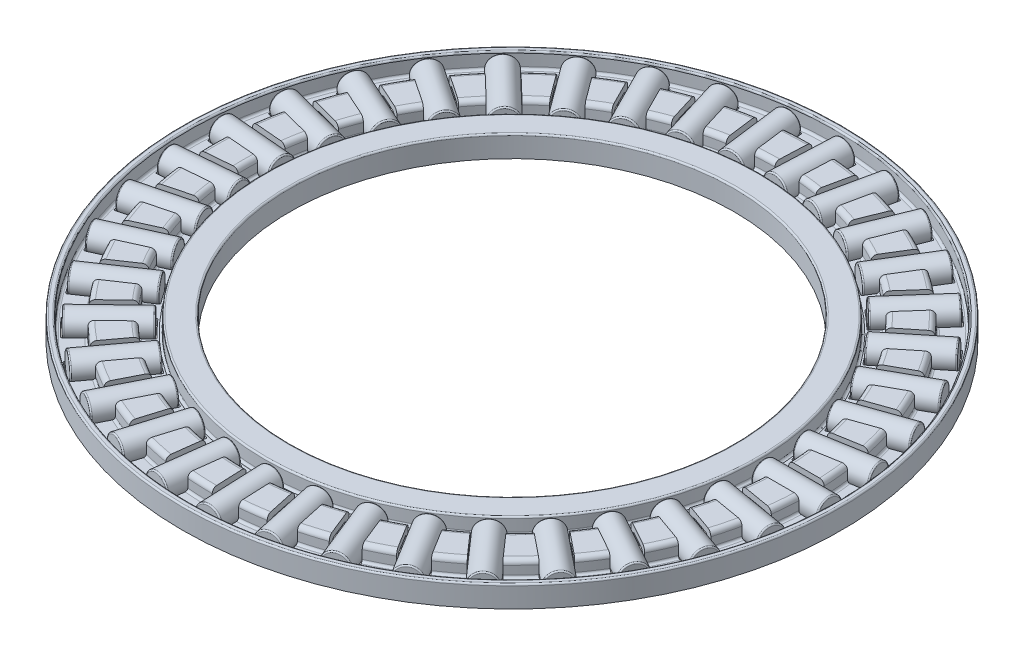
SolidWorks part; units mm, degrees
ref_plane "Front Plane" through (0, 0, 0) normal (0, 0, 1) x (1, 0, 0)
ref_plane "Top Plane" through (0, 0, 0) normal (0, 1, 0) x (1, 0, 0)
ref_plane "Right Plane" through (0, 0, 0) normal (1, 0, 0) x (0, 0, -1)
sketch "Sketch1" plane through (0, 0, 0) normal (1, 0, 0) x (0, 0, -1)
  line L0 (-26, 0) -> (26, 0) construction
  line L1 (-17.525, 0) -> (17.525, 0) construction
  line L2 (26, -1) -> (26, 1) construction
  line L3 (17.525, -0.85) -> (17.525, 0.85) construction
  line L4 (17.525, -0.85) -> (18.1833, -0.85) construction
  line L5 (18.1833, -0.85) -> (18.1833, 0.3734) construction
  line L6 (18.1833, 0.3734) -> (18.8417, 0.3734) construction
  line L7 (18.8417, 0.3734) -> (18.8417, -0.85) construction
  line L8 (18.8417, -0.85) -> (21.3311, -0.85) construction
  line L9 (21.3311, -0.85) -> (21.3311, 0.3734) construction
  line L10 (21.3311, 0.3734) -> (23.1772, 0.3734) construction
  line L11 (23.1772, 0.3734) -> (23.1772, -0.85) construction
  line L12 (23.1772, -0.85) -> (25.6667, -0.85) construction
  line L13 (25.6667, -0.85) -> (25.6667, 0.3734) construction
  line L14 (25.6667, 0.3734) -> (25.8333, 0.3734) construction
  line L15 (17.525, 0.85) -> (19.5, 0.85) construction
  line L16 (19.5, 0.85) -> (19.5, -0.3734) construction
  line L17 (19.5, -0.3734) -> (20.8545, -0.3734) construction
  line L18 (20.8545, -0.3734) -> (20.8545, 0.85) construction
  line L19 (20.8545, 0.85) -> (23.6538, 0.85) construction
  line L20 (23.6538, 0.85) -> (23.6538, -0.3734) construction
  line L21 (23.6538, -0.3734) -> (25.5, -0.3734) construction
  line L22 (25.5, -0.3734) -> (25.5, 0.85) construction
  line L23 (25.5, 0.85) -> (26, 0.85) construction
  line L24 (21.3311, 0.3734) -> (20.8545, 0.3734) construction
  line L25 (18.8417, 0.3734) -> (18.8417, 0.85) construction
  line L26 (23.1772, 0.3734) -> (23.6538, 0.3734) construction
  line L27 (19.5, -0.3734) -> (19.5, -0.85) construction
  line L28 (19.5, -0.3734) -> (18.8417, -0.3734) construction
  line L29 (25.6667, 0.3734) -> (25.5, 0.3734) construction
  line L30 (25.8333, 0.3734) -> (25.8333, -0.85) construction
  line L31 (25.8333, -0.85) -> (26, -0.85) construction
  line L32 (0, 1) -> (0, -1) construction
  line L33 (-19.5, 1) -> (19.5, 1) construction
  line L34 (-25.5, 0.85) -> (25.5, 0.85) construction
  line L35 (25.8333, 0.3734) -> (26, 0.3734) construction
  line L36 (20.8545, -0.3734) -> (20.8545, -0.85) construction
  line L37 (23.1772, 0.3734) -> (23.1772, 0.85) construction
  line L38 (18.1833, -0.3734) -> (17.525, -0.3734) construction
  line L39 (18.8417, -0.3734) -> (18.1833, -0.3734) construction
  point P4 (0, 0)
  point P8 (0, 0)
  point P11 (26, 0)
  point P14 (17.525, 0)
  point P45 (0, 1)
  point P48 (0, 0)
  point P49 (0, 1)
  point P55 (0, 0.85)
  dimension "OD" = 52
  dimension "ID" = 35.05
  dimension "Thickness" = 2
  dimension "Approx. Raceway Thickness" = 1.7
  dimension "Inner Raceway" = 39
  dimension "Outer Raceway" = 51
  dimension "Approx. Raceway Notch Width" = 1.8462
  dimension "D3" = 1.8462
sketch "Sketch2" plane through (0, 0, 0) normal (0, 1, 0) x (1, 0, 0)
  line L0 (19.5, 0) -> (25.5, 0) construction
  line L1 (25.2, 0) -> (19.8, 0)
  line L2 (25.1802, -1) -> (19.7747, -1)
  line L3 (25.1802, 1) -> (19.7747, 1)
  circle A0 centre (0, 0) radius 17.525
  circle A1 centre (0, 0) radius 19.5
  circle A2 centre (0, 0) radius 25.5
  circle A3 centre (0, 0) radius 26
  arc A4 (19.7747, -1) -> (19.7747, 1) centre (0, 0) ccw
  arc A5 (25.1802, -1) -> (25.1802, 1) centre (0, 0) ccw
  arc A6 (25.1802, 1) -> (25.0445, 2.795) centre (0, 0) ccw
  point P15 (22.5, 0)
  dimension "Approx. Roller Length" = 5.4
  dimension "Roller Thickness" = 2
  dimension "Roller Arc Length" = 2.0005
  dimension "Approx. Roller Gap" = 1.8005
sketch "Sketch3" plane through (0, 0, 0) normal (1, 0, 0) x (0, 0, -1)
  line L0 (18.1833, -0.85) -> (18.1833, 0.3734)
  line L1 (18.1833, 0.3734) -> (18.8417, 0.3734)
  line L2 (18.8417, 0.3734) -> (18.8417, -0.85)
  line L3 (18.8417, -0.85) -> (21.3311, -0.85)
  line L4 (21.3311, -0.85) -> (21.3311, 0.3734)
  line L5 (21.3311, 0.3734) -> (23.1772, 0.3734)
  line L6 (23.1772, 0.3734) -> (23.1772, -0.85)
  line L7 (23.1772, -0.85) -> (25.6667, -0.85)
  line L8 (25.6667, -0.85) -> (25.6667, 0.3734)
  line L9 (25.6667, 0.3734) -> (25.8333, 0.3734)
  line L10 (25.8333, 0.3734) -> (25.8333, -0.85)
  line L11 (25.8333, -0.85) -> (26, -0.85)
  line L12 (26, -0.85) -> (26, 0.85)
  line L13 (26, 0.85) -> (25.5, 0.85)
  line L14 (25.5, 0.85) -> (25.5, -0.3734)
  line L15 (25.5, -0.3734) -> (23.6538, -0.3734)
  line L16 (23.6538, -0.3734) -> (23.6538, 0.85)
  line L17 (23.6538, 0.85) -> (20.8545, 0.85)
  line L18 (20.8545, 0.85) -> (20.8545, -0.3734)
  line L19 (20.8545, -0.3734) -> (19.5, -0.3734)
  line L20 (19.5, -0.3734) -> (19.5, 0.85)
  line L21 (19.5, 0.85) -> (17.525, 0.85)
  line L22 (17.525, 0.85) -> (17.525, -0.85)
  line L23 (17.525, -0.85) -> (18.1833, -0.85)
revolve "Revolve1" add sketch "Sketch3" angle 360 about L32
fillet "Fillet1" radius 0.3692 4 edges at (0, -0.85, 23.1772) (0, -0.85, 25.6667) (0, -0.85, 18.8417) (0, -0.85, 21.3311)
fillet "Fillet2" radius 0.3692 2 edges at (0, 0.85, 23.6538) (0, 0.85, 20.8545)
fillet "Fillet3" radius 0.125 4 edges at (0, 0.85, 25.5) (0, 0.85, 26) (0, 0.85, 19.5) (0, 0.85, 17.525)
fillet "Fillet4" radius 0.1846 6 edges at (0, 0.3734, 21.3311) (0, 0.3734, 23.1772) (0, -0.3734, 25.5) (0, -0.3734, 23.6538) (0, -0.3734, 20.8545) (0, -0.3734, 19.5)
sketch "Sketch4" plane through (0, 0, 0) normal (0, 1, 0) x (1, 0, 0)
  line L0 (19.7747, 1) -> (25.1802, 1)
  line L1 (19.7747, -1) -> (25.1802, -1)
  arc A0 (19.7747, -1) -> (19.7747, 1) centre (0, 0) ccw construction
  arc A1 (19.7747, -1) -> (19.7747, 1) centre (0, 0) ccw
  arc A2 (25.1802, -1) -> (25.1802, 1) centre (0, 0) ccw construction
  arc A3 (25.1802, -1) -> (25.1802, 1) centre (0, 0) ccw
extrude "Cut-Extrude1" cut sketch "Sketch4" against normal through all both and the other way through all
fillet "Fillet5" radius 0.1 4 edges at (25.1802, -0.6117, -1) (25.1802, -0.6117, 1) (19.7747, -0.6117, -1) (19.7747, -0.6117, 1)
pattern_circular "CirPattern1" count 37 over 360 about axis through (0, 1, 0) along (0, -1, 0) of "Cut-Extrude1", "Fillet5"
sketch "Sketch5" plane through (0, 0, 0) normal (0, 1, 0) x (1, 0, 0)
  line L0 (19.8797, 0) -> (19.8797, 1)
  line L2 (19.8797, 1) -> (25.0838, 1)
  line L3 (25.0838, 1) -> (25.0838, 0)
  line L4 (25.0838, 0) -> (19.8797, 0)
  line L5 (25.2, 0) -> (19.8, 0) construction
revolve "Revolve2" add sketch "Sketch5" angle 360 about L1
fillet "Fillet6" radius 0.1 2 edges at (19.8797, 0, -1) (25.0838, 0, -1)
pattern_circular "CirPattern2" count 37 over 360 about axis through (0, 1, 0) along (0, -1, 0) of bodies 107
ref_axis "Center Axis 1" through (0, 1.65, 0) along (0, -1, 0)
ref_plane "Contact Plane 1" through (0, 1, 0) normal (0, 1, 0) x (1, 0, 0)
ref_plane "Contact Plane 2" through (0, -1, 0) normal (0, 1, 0) x (1, 0, 0)
equation "\"Approx. Raceway Thickness@Sketch1\" = \"Thickness@Sketch1\" * .85"
equation "\"Approx. Raceway Notch Width@Sketch1\" =  ( \"Outer Raceway@Sketch1\" - \"Inner Raceway@Sketch1\" )  / 6.5"
equation "\"D3@Sketch1\" = \"Approx. Raceway Notch Width@Sketch1\""
equation "\"D1@Fillet2\"=\"D1@Fillet1\""
equation "\"D1@Fillet3\"=(\"OD@Sketch1\"-\"Outer Raceway@Sketch1\")/8"
equation "\"D1@Fillet1\" = \"Approx. Raceway Notch Width@Sketch1\" * 2 / 10"
equation "\"D1@Fillet4\"=\"D1@Fillet2\"/2"
equation "\"Approx. Roller Length@Sketch2\" =  ( \"Outer Raceway@Sketch1\" - \"Inner Raceway@Sketch1\" )  / 2 * .9"
equation "\"Approx. Roller Gap@Sketch2\" = \"Roller Arc Length@Sketch2\" * .9"
equation "\"Raceway Diff\"= ( \"Outer Raceway@Sketch1\" - \"Inner Raceway@Sketch1\" )"
equation "\"Circumference\"= ( \"Inner Raceway@Sketch1\" + ( \"Raceway Diff\" / 2 ) ) * 3.14"
equation "\"Instances\"= int ( \"Circumference\" /  ( \"Roller Arc Length@Sketch2\" + \"Approx. Roller Gap@Sketch2\" )  ) "
equation "\"D1@CirPattern1\"=\"Instances\""
equation "\"D1@Fillet5\" = \"Roller Arc Length@Sketch2\" / 20"
equation "\"D1@Fillet6\" = \"Roller Arc Length@Sketch2\" / 20"
equation "\"D1@CirPattern2\" = \"D1@CirPattern1\""
equation "\"Roller Thickness@Sketch2\" = \"Thickness@Sketch1\""
